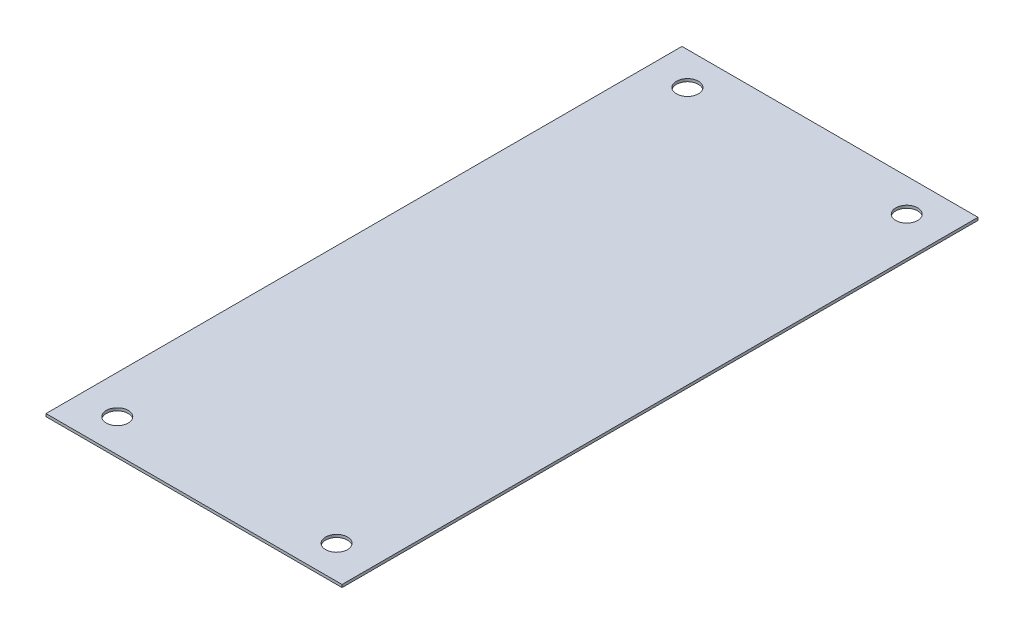
SolidWorks part; units mm, degrees
ref_plane "Front Plane" through (0, 0, 0) normal (0, 0, 1) x (1, 0, 0)
ref_plane "Top Plane" through (0, 0, 0) normal (0, 1, 0) x (1, 0, 0)
ref_plane "Right Plane" through (0, 0, 0) normal (1, 0, 0) x (0, 0, -1)
sketch "Sketch1" plane through (0, 0, 0) normal (0, 1, 0) x (1, 0, 0)
  line L1 (0, 0) -> (342.9, 0)
  line L2 (0, 0) -> (0, 736.6)
  line L3 (0, 736.6) -> (342.9, 736.6)
  line L4 (342.9, 0) -> (342.9, 736.6)
  dimension "D1" = 736.6
  dimension "D2" = 342.9
extrude "Boss-Extrude1" add sketch "Sketch1" along normal blind 3.175
hole_wizard "1 (1) Diameter Hole1" positions "Sketch3" profile "Sketch2" hole size "1" standard "Ansi Inch"
sketch "Sketch3" plane through (0, 3.175, 0) normal (0, 1, 0) x (-1, 0, 0)
  line L0 (0, 0) -> (-342.9, 0) construction
  line L1 (0, -368.3) -> (-342.9, -368.3) construction
  line L2 (0, -736.6) -> (0, 0) construction
  line L3 (-342.9, 0) -> (-342.9, -736.6) construction
  line L4 (-171.45, 0) -> (-171.45, -736.6) construction
  line L5 (-342.9, -736.6) -> (0, -736.6) construction
  line L6 (0, -736.6) -> (0, 0) construction
  point P0 (-44.45, -38.1)
  point P21 (-44.45, -698.5)
  point P23 (-298.45, -698.5)
  point P24 (-298.45, -38.1)
  dimension "D1" = 38.1
  dimension "D2" = 44.45
sketch "Sketch2" plane through (44.45, 3.175, -38.1) normal (1, 0, 0) x (0, 0, 1)
  line L0 (0, 0) -> (0, 28.2049)
  line L1 (0, 28.2049) -> (12.7, 20.574)
  line L2 (12.7, 20.574) -> (12.7, 0)
  line L5 (12.7, 0) -> (0, 0)
  line L10 (0, 28.2049) -> (-12.7, 20.574) construction
  line L11 (0, -6.35) -> (0, 107.95) construction
  dimension "Hole Dia." = 25.4
  dimension "Hole Depth" = 20.574
  dimension "Drill Angle" = 118
